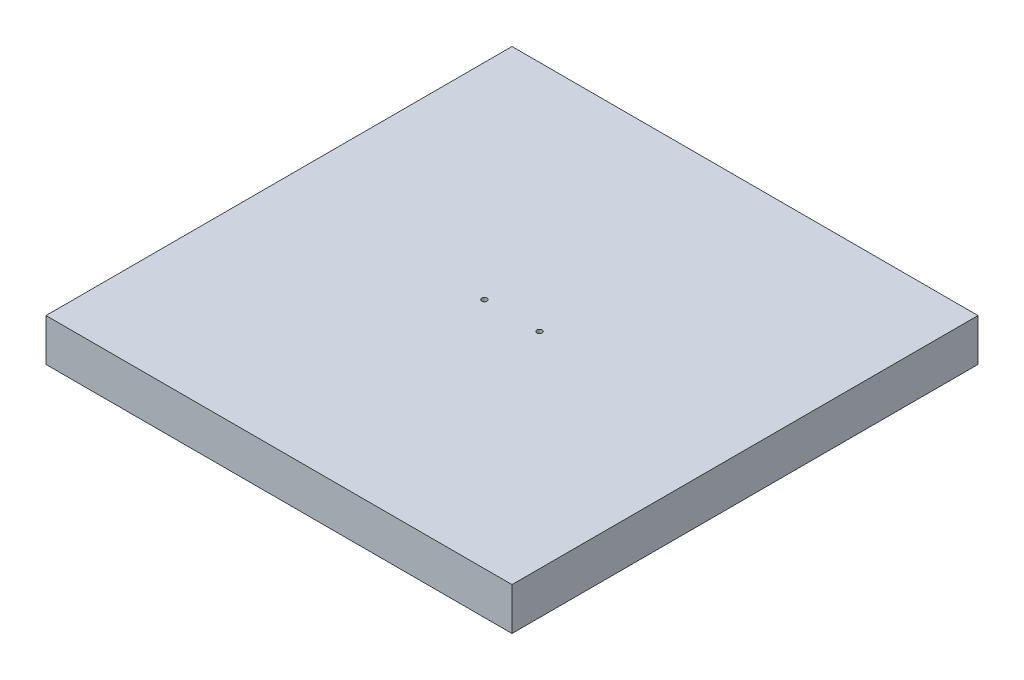
SolidWorks part; units mm, degrees
ref_plane "Front Plane" through (0, 0, 0) normal (0, 0, 1) x (1, 0, 0)
ref_plane "Top Plane" through (0, 0, 0) normal (0, 1, 0) x (1, 0, 0)
ref_plane "Right Plane" through (0, 0, 0) normal (1, 0, 0) x (0, 0, -1)
sketch "Sketch1" plane through (0, 0, 0) normal (0, 1, 0) x (1, 0, 0)
  line L1 (55, 55) -> (-55, 55)
  line L2 (55, 55) -> (55, -55)
  line L3 (55, -55) -> (-55, -55)
  line L4 (-55, 55) -> (-55, -55)
  line L5 (55, 55) -> (-55, -55) construction
  line L6 (55, -55) -> (-55, 55) construction
  point P0 (0, 0)
  dimension "D1" = 110
  dimension "D2" = 110
extrude "Boss-Extrude1" add sketch "Sketch1" along normal blind 10
hole_wizard "M1.6 Tapped Hole1" positions "Sketch3" profile "Sketch4" tap size "M1.6" standard "ISO" end condition through all
sketch "Sketch3" plane through (0, 10, 0) normal (0, 1, 0) x (1, 0, 0)
  line L0 (-55, 0) -> (55, 0)
  line L1 (-55, 55) -> (-55, -55) construction
  line L2 (55, -55) -> (55, 55) construction
  point P7 (-6.5, 0)
  point P9 (6.5, 0)
  dimension "D1" = 6.5
  dimension "D2" = 6.5
sketch "Sketch4" plane through (6.5, 10, 0) normal (1, 0, 0) x (0, 0, 1)
  line L0 (0, 0) -> (0, 10)
  line L1 (0, 10) -> (0.625, 10)
  line L2 (0.625, 10) -> (0.625, 0)
  line L5 (0.625, 0) -> (0, 0)
  line L11 (0, -6.35) -> (0, 107.95) construction
  dimension "Thru Tap Drill Dia." = 1.25
  dimension "Thru Tap Drill Depth" = 10
cosmetic thread "Hole Thread5" parameters "D1"=10, "D2"=2.25
cosmetic thread "Hole Thread6" parameters "D1"=10, "D2"=2.25
sketch "Sketch5" plane through (0, 10, 0) normal (0, 1, 0) x (1, 0, 0)
  line L1 (20, 20) -> (-20, 20)
  line L2 (20, 20) -> (20, -20)
  line L3 (20, -20) -> (-20, -20)
  line L4 (-20, 20) -> (-20, -20)
  line L5 (20, 20) -> (-20, -20) construction
  line L6 (20, -20) -> (-20, 20) construction
  point P0 (0, 0)
  dimension "D1" = 40
  dimension "D2" = 40
extrude "Boss-Extrude2" [suppressed] add sketch "Sketch5" along normal blind 10
